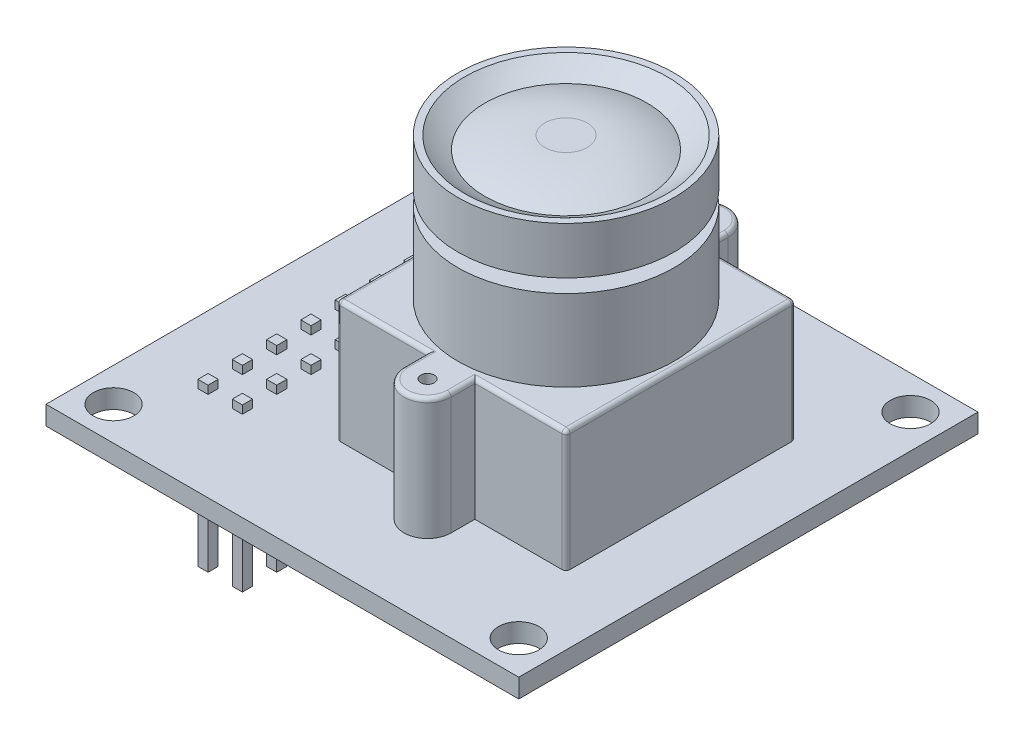
SolidWorks part; units mm, degrees
ref_plane "Front Plane" through (0, 0, 0) normal (0, 0, 1) x (1, 0, 0)
ref_plane "Top Plane" through (0, 0, 0) normal (0, 1, 0) x (1, 0, 0)
ref_plane "Right Plane" through (0, 0, 0) normal (1, 0, 0) x (0, 0, -1)
sketch "Sketch1" plane through (0, 0, 0) normal (0, 1, 0) x (1, 0, 0)
  line L1 (-19.2335, 8.5) -> (15.7665, 8.5)
  line L2 (-19.2335, 8.5) -> (-19.2335, -25.5)
  line L3 (-19.2335, -25.5) -> (15.7665, -25.5)
  line L4 (15.7665, 8.5) -> (15.7665, -25.5)
  circle A0 centre (-16.7335, 6) radius 1.5
  circle A1 centre (-16.7335, -23) radius 1.5
  circle A2 centre (13.2665, 6) radius 1.5
  circle A3 centre (13.2665, -23) radius 1.5
  dimension "D3" = 3
  dimension "D1" = 35
  dimension "D2" = 34
  dimension "D4" = 2.5
  dimension "D5" = 2.5
  dimension "D6" = 2.5
  dimension "D7" = 2.5
  dimension "D8" = 2.5
  dimension "D9" = 2.5
  dimension "D10" = 2.5
  dimension "D11" = 2.5
extrude "Boss-Extrude1" add sketch "Sketch1" along normal blind 1.4
sketch "Sketch2" plane through (0, 1.4, 0) normal (0, 1, 0) x (1, 0, 0)
  line L0 (15.7665, -25.5) -> (15.7665, 8.5) construction
  line L1 (-6.2335, 0) -> (0.5165, 0)
  line L2 (-6.2335, 0) -> (-6.2335, -17)
  line L3 (-6.2335, -17) -> (0.5165, -17)
  line L4 (10.7665, 0) -> (10.7665, -17)
  line L5 (-19.2335, -25.5) -> (15.7665, -25.5) construction
  line L6 (-0.2335, -14.9296) -> (-0.2335, -19.9748) construction
  line L7 (4.7665, -14.9296) -> (4.7665, -19.9748) construction
  line L8 (0.5165, -18.75) -> (0.5165, -17)
  line L9 (4.0165, -18.75) -> (4.0165, -17)
  line L10 (4.0165, -17) -> (10.7665, -17)
  line L11 (-6.2335, -8.5) -> (10.7665, -8.5) construction
  line L12 (4.0165, 1.75) -> (4.0165, 0)
  line L13 (0.5165, 1.75) -> (0.5165, 0)
  line L14 (4.0165, 0) -> (10.7665, 0)
  arc A0 (0.5165, -18.75) -> (4.0165, -18.75) centre (2.2665, -18.75) ccw
  arc A1 (0.5165, 1.75) -> (4.0165, 1.75) centre (2.2665, 1.75) cw
  circle A2 centre (2.2665, 1.75) radius 0.5
  circle A3 centre (2.2665, -18.75) radius 0.5
  dimension "D7" = 3.5
  dimension "D8" = 1
  dimension "D9" = 1
  dimension "D1" = 17
  dimension "D2" = 17
  dimension "D3" = 5
  dimension "D4" = 8.5
  dimension "D5" = 6
  dimension "D6" = 6
extrude "Boss-Extrude2" add sketch "Sketch2" along normal blind 9
sketch "Sketch3" plane through (0, 10.4, 0) normal (0, 1, 0) x (1, 0, 0)
  line L0 (2.2665, -8.5) -> (-10.8138, -8.5) construction
  line L1 (-6.2335, 0) -> (-6.2335, -17) construction
  line L2 (-6.2335, -9.5) -> (-5.6707, -9.5)
  line L3 (-6.2335, -9.5) -> (-6.2335, -7.5)
  line L4 (-6.2335, -7.5) -> (-5.6707, -7.5)
  line L6 (4.0165, -17) -> (10.7665, -17) construction
  line L7 (10.7665, 0) -> (4.0165, 0) construction
  arc A0 (-5.6707, -9.5) -> (-5.6707, -7.5) centre (2.2665, -8.5) ccw
  dimension "D1" = 16
  dimension "D2" = 1
  dimension "D3" = 8.5
  dimension "D4" = 8.5
  dimension "D5" = 1
extrude "Boss-Extrude3" add sketch "Sketch3" along normal blind 6
sketch "Sketch4" plane through (0, 16.4, 0) normal (0, 1, 0) x (1, 0, 0)
  circle A0 centre (2.2665, -8.5) radius 6
  dimension "D1" = 12
extrude "Boss-Extrude4" add sketch "Sketch4" along normal blind 1
sketch "Sketch5" plane through (0, 17.4, 0) normal (0, 1, 0) x (1, 0, 0)
  circle A0 centre (2.2665, -8.5) radius 8
  dimension "D1" = 16
extrude "Boss-Extrude5" add sketch "Sketch5" along normal blind 3.5
sketch "Sketch6" plane through (0, 20.9, 0) normal (0, 1, 0) x (1, 0, 0)
  circle A0 centre (2.2665, -8.5) radius 7.5
  dimension "D1" = 15
extrude "Cut-Extrude1" cut sketch "Sketch6" against normal blind 2
fillet "Fillet1" radius 10 1 edges at (2.2665, 18.9, 16)
sketch "Sketch7" plane through (0, 18.9, 0) normal (0, 1, 0) x (1, 0, 0)
  circle A0 centre (2.2665, -8.5) radius 6
  dimension "D1" = 12
extrude "Boss-Extrude6" add sketch "Sketch7" along normal blind 2
fillet "Fillet2" radius 11 1 edges at (2.2665, 20.9, 14.5)
fillet "Fillet3" radius 0.3 17 edges at (-2.8585, 10.4, 0) (0.5165, 10.4, -0.875) (2.2665, 10.4, -3.5) (4.0165, 10.4, -0.875) (7.3915, 10.4, 0) (10.7665, 10.4, 8.5) (7.3915, 10.4, 17) (4.0165, 10.4, 17.875) (2.2665, 10.4, 20.5) (0.5165, 10.4, 17.875) (-2.8585, 10.4, 17) (-6.2335, 10.4, 13.25) (-6.2335, 10.4, 3.75) (-6.2335, 5.9, 0) (-6.2335, 5.9, 17) (10.7665, 5.9, 0) (10.7665, 5.9, 17)
sketch "Sketch8" plane through (-6.2335, 0, 0) normal (-1, 0, 0) x (0, 0, 1)
  line L0 (7.5, 16.4) -> (7.5, 10.1) construction
  line L1 (9.5, 16.4) -> (9.5, 10.1) construction
  line L2 (7.5, 16.4) -> (9.5, 16.4) construction
  circle A0 centre (8.5, 13.9) radius 0.5
  dimension "D1" = 1
  dimension "D2" = 1
  dimension "D3" = 1
  dimension "D4" = 2.5
extrude "Cut-Extrude2" cut sketch "Sketch8" against normal blind 0.5
sketch "Sketch9" plane through (0, 0, 0) normal (0, -1, 0) x (1, 0, 0)
  line L0 (-14.2335, 18.5) -> (-14.2335, 19.4314) construction
  line L1 (-14.6085, 18.875) -> (-13.8585, 18.875)
  line L2 (-14.6085, 18.875) -> (-14.6085, 18.125)
  line L3 (-14.6085, 18.125) -> (-13.8585, 18.125)
  line L4 (-13.8585, 18.875) -> (-13.8585, 18.125)
  line L5 (-12.0685, 18.875) -> (-11.3185, 18.875)
  line L6 (-12.0685, 18.875) -> (-12.0685, 18.125)
  line L7 (-12.0685, 18.125) -> (-11.3185, 18.125)
  line L8 (-11.3185, 18.875) -> (-11.3185, 18.125)
  line L9 (-11.6935, 18.5) -> (-11.6935, 19.4314) construction
  line L11 (-19.2335, -8.5) -> (-19.2335, 25.5) construction
  line L12 (-19.2335, 25.5) -> (15.7665, 25.5) construction
  line L13 (-14.6085, 16.335) -> (-13.8585, 16.335)
  line L14 (-14.6085, 16.335) -> (-14.6085, 15.585)
  line L15 (-14.6085, 15.585) -> (-13.8585, 15.585)
  line L16 (-13.8585, 16.335) -> (-13.8585, 15.585)
  line L17 (-12.0685, 16.335) -> (-11.3185, 16.335)
  line L18 (-12.0685, 16.335) -> (-12.0685, 15.585)
  line L19 (-12.0685, 15.585) -> (-11.3185, 15.585)
  line L20 (-11.3185, 16.335) -> (-11.3185, 15.585)
  line L21 (-14.6085, 13.795) -> (-13.8585, 13.795)
  line L22 (-14.6085, 13.795) -> (-14.6085, 13.045)
  line L23 (-14.6085, 13.045) -> (-13.8585, 13.045)
  line L24 (-13.8585, 13.795) -> (-13.8585, 13.045)
  line L25 (-12.0685, 13.795) -> (-11.3185, 13.795)
  line L26 (-12.0685, 13.795) -> (-12.0685, 13.045)
  line L27 (-12.0685, 13.045) -> (-11.3185, 13.045)
  line L28 (-11.3185, 13.795) -> (-11.3185, 13.045)
  line L29 (-14.6085, 11.255) -> (-13.8585, 11.255)
  line L30 (-14.6085, 11.255) -> (-14.6085, 10.505)
  line L31 (-14.6085, 10.505) -> (-13.8585, 10.505)
  line L32 (-13.8585, 11.255) -> (-13.8585, 10.505)
  line L33 (-12.0685, 11.255) -> (-11.3185, 11.255)
  line L34 (-12.0685, 11.255) -> (-12.0685, 10.505)
  line L35 (-12.0685, 10.505) -> (-11.3185, 10.505)
  line L36 (-11.3185, 11.255) -> (-11.3185, 10.505)
  line L37 (-14.6085, 8.715) -> (-13.8585, 8.715)
  line L38 (-14.6085, 8.715) -> (-14.6085, 7.965)
  line L39 (-14.6085, 7.965) -> (-13.8585, 7.965)
  line L40 (-13.8585, 8.715) -> (-13.8585, 7.965)
  line L41 (-12.0685, 8.715) -> (-11.3185, 8.715)
  line L42 (-12.0685, 8.715) -> (-12.0685, 7.965)
  line L43 (-12.0685, 7.965) -> (-11.3185, 7.965)
  line L44 (-11.3185, 8.715) -> (-11.3185, 7.965)
  line L45 (-14.6085, 6.175) -> (-13.8585, 6.175)
  line L46 (-14.6085, 6.175) -> (-14.6085, 5.425)
  line L47 (-14.6085, 5.425) -> (-13.8585, 5.425)
  line L48 (-13.8585, 6.175) -> (-13.8585, 5.425)
  line L49 (-12.0685, 6.175) -> (-11.3185, 6.175)
  line L50 (-12.0685, 6.175) -> (-12.0685, 5.425)
  line L51 (-12.0685, 5.425) -> (-11.3185, 5.425)
  line L52 (-11.3185, 6.175) -> (-11.3185, 5.425)
  line L53 (-14.6085, 3.635) -> (-13.8585, 3.635)
  line L54 (-14.6085, 3.635) -> (-14.6085, 2.885)
  line L55 (-14.6085, 2.885) -> (-13.8585, 2.885)
  line L56 (-13.8585, 3.635) -> (-13.8585, 2.885)
  line L57 (-12.0685, 3.635) -> (-11.3185, 3.635)
  line L58 (-12.0685, 3.635) -> (-12.0685, 2.885)
  line L59 (-12.0685, 2.885) -> (-11.3185, 2.885)
  line L60 (-11.3185, 3.635) -> (-11.3185, 2.885)
  line L61 (-14.6085, 1.095) -> (-13.8585, 1.095)
  line L62 (-14.6085, 1.095) -> (-14.6085, 0.345)
  line L63 (-14.6085, 0.345) -> (-13.8585, 0.345)
  line L64 (-13.8585, 1.095) -> (-13.8585, 0.345)
  line L65 (-12.0685, 1.095) -> (-11.3185, 1.095)
  line L66 (-12.0685, 1.095) -> (-12.0685, 0.345)
  line L67 (-12.0685, 0.345) -> (-11.3185, 0.345)
  line L68 (-11.3185, 1.095) -> (-11.3185, 0.345)
  line L69 (-14.6085, -1.445) -> (-13.8585, -1.445)
  line L70 (-14.6085, -1.445) -> (-14.6085, -2.195)
  line L71 (-14.6085, -2.195) -> (-13.8585, -2.195)
  line L72 (-13.8585, -1.445) -> (-13.8585, -2.195)
  line L73 (-12.0685, -1.445) -> (-11.3185, -1.445)
  line L74 (-12.0685, -1.445) -> (-12.0685, -2.195)
  line L75 (-12.0685, -2.195) -> (-11.3185, -2.195)
  line L76 (-11.3185, -1.445) -> (-11.3185, -2.195)
  line L77 (-14.6085, 18.875) -> (-14.6085, 16.335) construction
  dimension "D1" = 0.75
  dimension "D2" = 0.75
  dimension "D3" = 0.75
  dimension "D4" = 0.75
  dimension "D5" = 2.54
  dimension "D6" = 0.375
  dimension "D7" = 0.375
  dimension "D8" = 0.375
  dimension "D9" = 7
  dimension "D10" = 5
  dimension "D12" = 2.54
  dimension "D11" = 9
extrude "Boss-Extrude7" add sketch "Sketch9" along normal blind 10 and the other way blind 2
sketch "Sketch10" plane through (0, 0, 0) normal (0, -1, 0) x (1, 0, 0)
  line L0 (-14.6085, 18.875) -> (-13.8585, 18.875) construction
  line L1 (-15.6085, 19.875) -> (-10.3185, 19.875)
  line L2 (-15.6085, 19.875) -> (-15.6085, -3.195)
  line L3 (-15.6085, -3.195) -> (-10.3185, -3.195)
  line L4 (-10.3185, 19.875) -> (-10.3185, -3.195)
  line L5 (-14.6085, 18.125) -> (-14.6085, 18.875) construction
  line L6 (-11.3185, 18.125) -> (-11.3185, 18.875) construction
  line L7 (-11.3185, 18.875) -> (-12.0685, 18.875) construction
  line L8 (-11.3185, -2.195) -> (-12.0685, -2.195) construction
  line L9 (-11.3185, -1.445) -> (-11.3185, -2.195) construction
  dimension "D1" = 1
  dimension "D2" = 1
  dimension "D3" = 1
  dimension "D4" = 1
  dimension "D5" = 1
  dimension "D6" = 1
extrude "Boss-Extrude8" add sketch "Sketch10" along normal blind 3
fillet "Fillet4" radius 1 4 edges at (-15.6085, -1.5, -3.195) (-10.3185, -1.5, -3.195) (-10.3185, -1.5, 19.875) (-15.6085, -1.5, 19.875)
